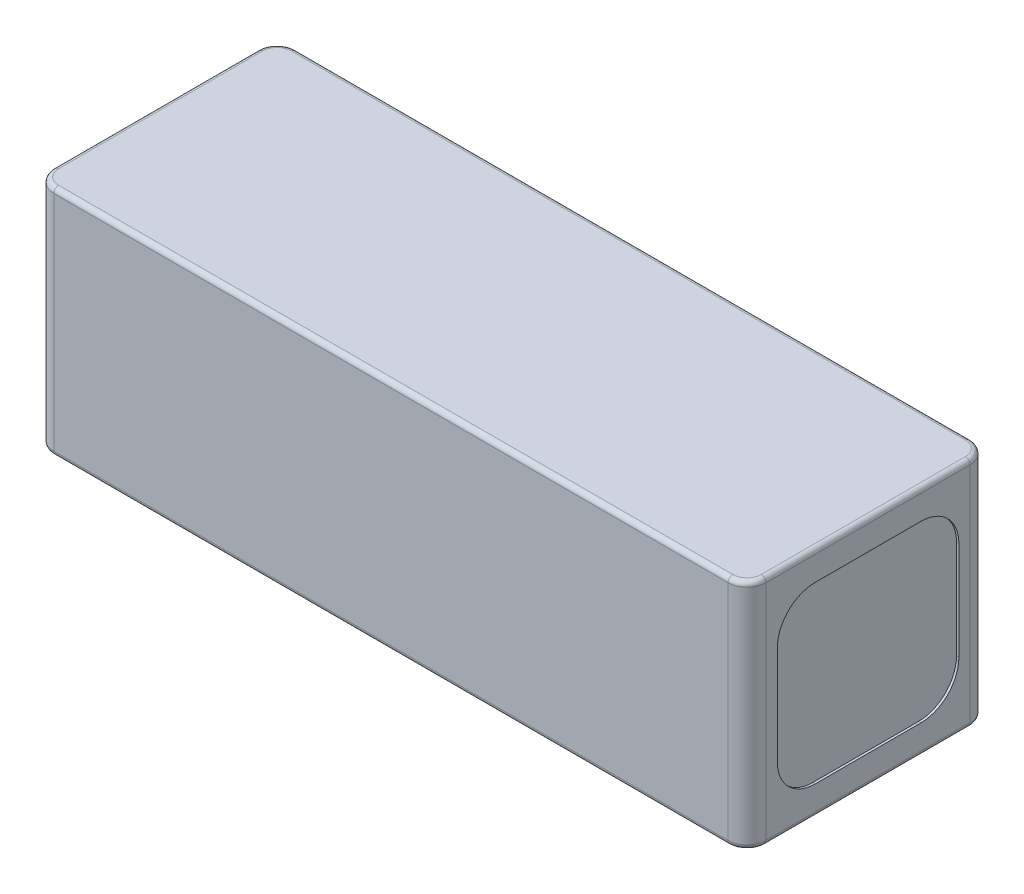
SolidWorks part; units mm, degrees
ref_plane "Front Plane" through (0, 0, 0) normal (0, 0, 1) x (1, 0, 0)
ref_plane "Top Plane" through (0, 0, 0) normal (0, 1, 0) x (1, 0, 0)
ref_plane "Right Plane" through (0, 0, 0) normal (1, 0, 0) x (0, 0, -1)
ref_plane "Plane1" through (0, 0, -15) normal (0, 0, -1) x (-1, 0, 0)
sketch "Sketch1" plane through (0, 0, -15) normal (0, 0, -1) x (-1, 0, 0)
  line L0 (-69, -22) -> (81, -22)
  line L1 (81, -22) -> (81, 27)
  line L2 (81, 27) -> (-69, 27)
  line L3 (-69, 27) -> (-69, -22)
  line L4 (-69, 2.5) -> (81, 2.5) construction
  line L5 (6, 27) -> (6, -22) construction
  dimension "D1" = 49
  dimension "D2" = 150
extrude "Boss-Extrude1" add sketch "Sketch1" against normal blind 51
sketch "Sketch2" plane through (69, 0, 0) normal (1, 0, 0) x (0, 0, -1)
  line L0 (-29.625, 12.875) -> (-29.625, -7.875)
  line L1 (-21.625, -15.875) -> (0.625, -15.875)
  line L2 (8.625, -7.875) -> (8.625, 12.875)
  line L3 (0.625, 20.875) -> (-21.625, 20.875)
  line L4 (-36, 27) -> (15, -22) construction
  line L5 (15, 27) -> (-36, -22) construction
  line L6 (-29.625, 20.875) -> (8.625, -15.875) construction
  line L7 (8.625, 20.875) -> (-29.625, -15.875) construction
  line L12 (-36, 27) -> (15, 27) construction
  line L13 (-36, 27) -> (-36, -22) construction
  line L14 (-36, -22) -> (15, -22) construction
  line L15 (15, 27) -> (15, -22) construction
  line L16 (-36, 27) -> (15, -22) construction
  line L17 (-36, -22) -> (15, 27) construction
  arc A0 (-29.625, -7.875) -> (-21.625, -15.875) centre (-21.625, -7.875) ccw
  arc A1 (0.625, -15.875) -> (8.625, -7.875) centre (0.625, -7.875) ccw
  arc A2 (8.625, 12.875) -> (0.625, 20.875) centre (0.625, 12.875) ccw
  arc A3 (-29.625, 12.875) -> (-21.625, 20.875) centre (-21.625, 12.875) cw
  point P16 (-10.5, 2.5)
  dimension "D3" = 8
  dimension "D1" = 38.25
  dimension "D2" = 51
extrude "Cut-Extrude1" cut sketch "Sketch2" against normal blind 0.5
sketch "Sketch3" plane through (-81, 0, 0) normal (-1, 0, 0) x (0, 0, 1)
  line L0 (21.625, 20.875) -> (-0.625, 20.875)
  line L1 (-8.625, 12.875) -> (-8.625, -7.875)
  line L2 (-0.625, -15.875) -> (21.625, -15.875)
  line L3 (29.625, -7.875) -> (29.625, 12.875)
  line L4 (-8.625, 20.875) -> (29.625, -15.875) construction
  line L5 (29.625, 20.875) -> (-8.625, -15.875) construction
  line L6 (-15, 27) -> (36, -22) construction
  line L7 (36, -22) -> (-15, -22) construction
  line L8 (-15, -22) -> (36, 27) construction
  arc A0 (-8.625, -7.875) -> (-0.625, -15.875) centre (-0.625, -7.875) ccw
  arc A1 (21.625, -15.875) -> (29.625, -7.875) centre (21.625, -7.875) ccw
  arc A2 (21.625, 20.875) -> (29.625, 12.875) centre (21.625, 12.875) cw
  arc A3 (-0.625, 20.875) -> (-8.625, 12.875) centre (-0.625, 12.875) ccw
  dimension "D3" = 8
  dimension "D1" = 38.25
  dimension "D2" = 51
extrude "Cut-Extrude2" cut sketch "Sketch3" against normal blind 0.5
fillet "Fillet1" radius 4 4 edges at (-81, 2.5, -15) (-81, 2.5, 36) (69, 2.5, -15) (69, 2.5, 36) tangent propagation no
fillet "Fillet2" radius 1 16 edges at (67.8284, 27, -13.8284) (69, 27, 10.5) (-6, 27, -15) (67.8284, 27, 34.8284) (-79.8284, 27, -13.8284) (-6, 27, 36) (-81, 27, 10.5) (-79.8284, 27, 34.8284) (-81, -22, 10.5) (-79.8284, -22, -13.8284) (-79.8284, -22, 34.8284) (-6, -22, -15) (-6, -22, 36) (67.8284, -22, -13.8284) (67.8284, -22, 34.8284) (69, -22, 10.5) tangent propagation no
sketch "Sketch4" plane through (0, 0, 36) normal (0, 0, 1) x (1, 0, 0)
  line L0 (-77, 2.5) -> (65, 2.5) construction
  line L1 (-77, 26) -> (-77, -21) construction
  line L2 (65, -21) -> (65, 26) construction
  line L3 (-6, 25.9735) -> (-6, -21) construction
  line L4 (-77, -21) -> (65, -21) construction
  circle A0 centre (-6, 2.5) radius 0.5026
equation "\"D1@Sketch3\"=\"D2@Sketch3\" * .75"
equation "\"D1@Sketch2\"=\"D2@Sketch2\"* .75"
